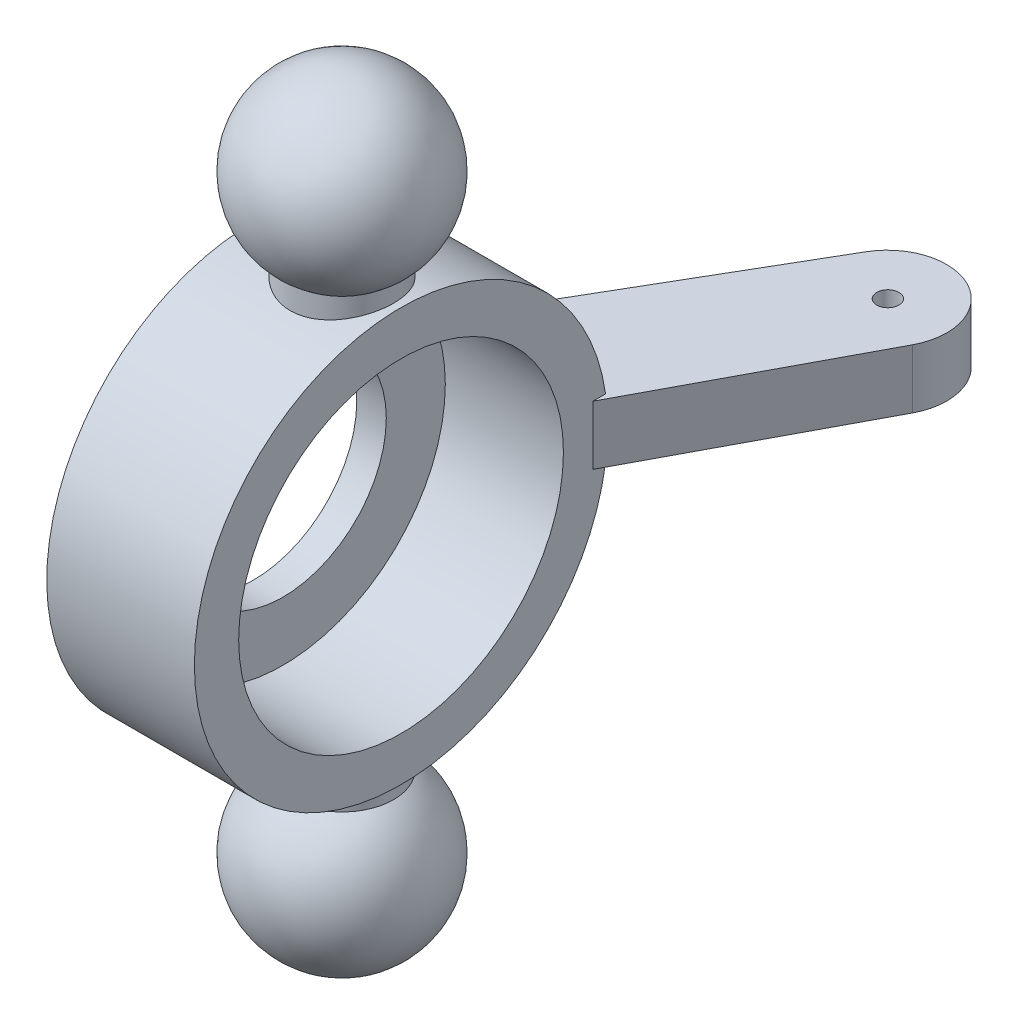
SolidWorks part; units mm, degrees
ref_plane "Front Plane" through (0, 0, 0) normal (0, 0, 1) x (1, 0, 0)
ref_plane "Top Plane" through (0, 0, 0) normal (0, 1, 0) x (1, 0, 0)
ref_plane "Right Plane" through (0, 0, 0) normal (1, 0, 0) x (0, 0, -1)
sketch "Sketch1" plane through (0, 0, 0) normal (1, 0, 0) x (0, 0, -1)
  circle A0 centre (0, 0) radius 11
  circle A1 centre (0, 0) radius 14
  dimension "D1" = 22
  dimension "D2" = 3
extrude "Boss-Extrude1" add sketch "Sketch1" along normal blind 8
ref_plane "Plane1" through (4, 0, 0) normal (1, 0, 0) x (0, 0, -1)
sketch "Sketch2" plane through (4, 0, 0) normal (1, 0, 0) x (0, 0, -1)
  line L0 (0, 12) -> (0, 20) construction
  line L2 (0, 12) -> (3.5, 12)
  line L3 (0, 12) -> (0, 20)
  line L4 (0, 20) -> (3.5, 20)
  line L5 (3.5, 12) -> (3.5, 20)
  circle A0 centre (0, 0) radius 11 construction
  dimension "D1" = 3.5
  dimension "D2" = 12
  dimension "D3" = 8
revolve "Revolve1" add sketch "Sketch2" angle 360 about L0
sketch "Sketch3" plane through (4, 0, 0) normal (1, 0, 0) x (0, 0, -1)
  line L0 (3.5, 20) -> (-3.5, 20) construction
  line L1 (0, 14) -> (0, 26)
  arc A0 (0, 14) -> (0, 26) centre (0, 20) ccw
  dimension "D1" = 6
revolve "Revolve2" add sketch "Sketch3" angle 360 about L1 region at (4, 20, -2.5465)
mirror "Mirror1" about plane through (0, 0, 0) normal (0, 1, 0) of "Revolve2", "Revolve1"
sketch "Sketch4" plane through (8, 0, 0) normal (1, 0, 0) x (0, 0, -1)
  circle A0 centre (0, 0) radius 14
  circle A1 centre (0, 0) radius 7
  dimension "D1" = 14
  dimension "D2" = 28
extrude "Boss-Extrude2" add sketch "Sketch4" along normal blind 2
sketch "Sketch5" plane through (0, 0, 0) normal (0, 1, 0) x (1, 0, 0)
  line L0 (10, -14) -> (10, 14) construction
  line L1 (10, 13) -> (0, 13)
  line L5 (10, 14) -> (0, 14) construction
  line L11 (10, 13) -> (-0.4773, 31.0113)
  line L12 (-3.9349, 33) -> (-3.9771, 33)
  line L13 (-7.5089, 27.1221) -> (0, 13)
  line L14 (0, 14) -> (0, -14) construction
  line L15 (5, 13) -> (-5.9343, 32.4884) construction
  arc A3 (-3.9771, 33) -> (-7.5089, 27.1221) centre (-3.9771, 29) ccw
  arc A4 (-0.4773, 31.0113) -> (-3.9349, 33) centre (-3.9349, 29) ccw
  circle A5 centre (-3.9771, 29) radius 0.75
  point P13 (-10.6342, 33)
  point P16 (-1.6342, 33)
  dimension "D5" = 0
  dimension "D6" = 4
  dimension "D3" = 20
  dimension "D7" = 1.5
  dimension "D1" = 1
  dimension "D2" = 9
  dimension "D4" = 152
extrude "Boss-Extrude3" add sketch "Sketch5" along normal blind 2 and the other way blind 2
mirror "Mirror2" about plane through (10, 0, 0) normal (1, 0, 0) of bodies 106
delete or keep bodies "Body-Delete/Keep 1" type delete bodies bodies 106
